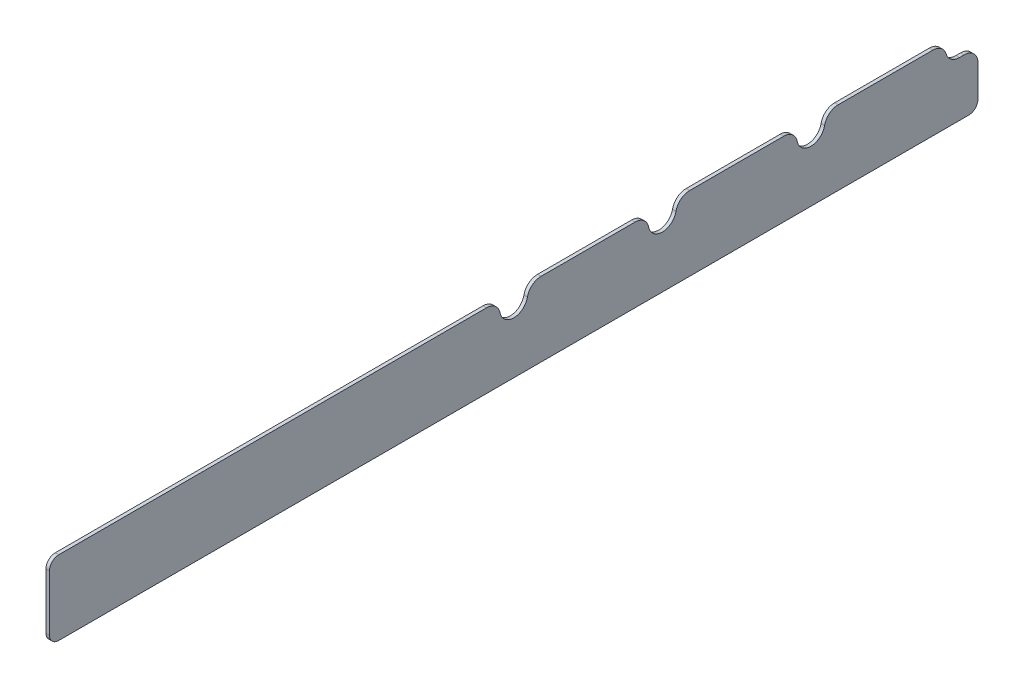
SolidWorks part; units mm, degrees
material "Plain Carbon Steel"
ref_plane "Front" through (0, 0, 0) normal (0, 0, 1) x (1, 0, 0)
ref_plane "Top" through (0, 0, 0) normal (0, 1, 0) x (1, 0, 0)
ref_plane "Right" through (0, 0, 0) normal (1, 0, 0) x (0, 0, -1)
sketch "Sketch1" plane through (0, 0, 0) normal (1, 0, 0) x (0, 0, -1)
  line L1 (-158.75, -12.7) -> (158.75, -12.7)
  line L2 (-158.75, -12.7) -> (-158.75, 12.7)
  line L3 (-158.75, 12.7) -> (158.75, 12.7)
  line L4 (158.75, -12.7) -> (158.75, 12.7)
  line L5 (-158.75, -12.7) -> (158.75, 12.7) construction
  line L6 (-158.75, 12.7) -> (158.75, -12.7) construction
  point P0 (0, 0)
  dimension "D1" = 25.4
  dimension "D2" = 317.5
base flange "Base-Flange1" sketch "Sketch1" thickness 1.1938 reverse thickness direction no parameters "D1"=1.4986
fillet "Fillet1" radius 3.175 4 edges at (-0.5969, 12.7, -158.75) (-0.5969, -12.7, 158.75) (-0.5969, -12.7, -158.75) (-0.5969, 12.7, 158.75)
sketch "Sketch2" plane through (-1.1938, 0, 0) normal (-1, 0, 0) x (0, 0, 1)
  line L0 (-155.575, 12.7) -> (155.575, 12.7) construction
  line L1 (-4.7625, 9.8298) -> (-4.7625, 12.7)
  line L2 (4.7625, 9.8298) -> (4.7625, 12.7)
  line L3 (-4.7625, 12.7) -> (4.7625, 12.7)
  arc A0 (-4.7625, 9.8298) -> (4.7625, 9.8298) centre (0, 9.8298) ccw
  arc A1 (3.8004, 12.7) -> (-3.8004, 12.7) centre (0, 9.8298) ccw construction
  arc A2 (-3.8004, 12.7) -> (-4.7625, 9.8298) centre (0, 9.8298) ccw construction
  arc A3 (4.7625, 9.8298) -> (3.8004, 12.7) centre (0, 9.8298) ccw construction
  point P1 (-10.9415, 9.8298)
  point P3 (0, 0)
  dimension "D3" = 9.525
  dimension "D1" = 2.8702
extrude "Cut-Extrude1" cut sketch "Sketch2" against normal through all normal cut yes
fillet "Fillet2" radius 4.7625 2 edges at (-0.5969, 12.7, 4.7625) (-0.5969, 12.7, -4.7625)
pattern_linear "LPattern2" count 3 spacing 50.8 along (0, 0, -1) of "Cut-Extrude1", "Fillet2"
sketch "Sketch3" plane through (-1.1938, 0, 0) normal (-1, 0, 0) x (0, 0, 1)
  line L0 (-155.575, 12.7) -> (-110.9351, 12.7) construction
  line L1 (-152.4, 5.9512) -> (-158.75, 5.9512)
  line L2 (-158.75, -9.525) -> (-158.75, 9.525) construction
  line L3 (-147.6375, 10.7137) -> (-147.6375, 12.7)
  line L4 (-155.575, 12.7) -> (-147.6375, 12.7)
  line L5 (-158.75, 5.9512) -> (-158.75, 9.525)
  line L6 (-147.6375, 12.7) -> (-110.9351, 12.7) construction
  line L7 (-158.75, -9.525) -> (-158.75, 5.9512) construction
  arc A0 (-152.4, 5.9512) -> (-147.6375, 10.7137) centre (-152.4, 10.7137) ccw
  arc A2 (-155.575, 12.7) -> (-158.75, 9.525) centre (-155.575, 9.525) ccw construction
  arc A3 (-155.575, 12.7) -> (-158.75, 9.525) centre (-155.575, 9.525) ccw
  arc A4 (-154.6162, 6.4982) -> (-152.4, 5.9512) centre (-152.4, 10.7137) ccw construction
  arc A5 (-148.0715, 12.7) -> (-154.6162, 6.4982) centre (-152.4, 10.7137) ccw construction
  arc A6 (-147.6375, 10.7137) -> (-148.0715, 12.7) centre (-152.4, 10.7137) ccw construction
  arc A7 (-106.2676, 8.8836) -> (-96.9324, 8.8836) centre (-101.6, 9.8298) ccw construction
  point P10 (-101.6, 5.0673)
  dimension "D2" = 9.525
  dimension "D1" = 1.9863
  dimension "D3" = 50.8
extrude "Cut-Extrude2" cut sketch "Sketch3" against normal through all normal cut yes
fillet "Fillet3" radius 4.7625 2 edges at (-0.5969, 5.9512, -158.75) (-0.5969, 12.7, -147.6375)
sketch "Bend-Lines1" [suppressed] plane through (0, 0, 0) normal (0, 1, 0) x (1, 0, 0)
sketch "Bounding-Box1" [suppressed] plane through (0, 0, 0) normal (0, 1, 0) x (1, 0, 0)
sheet metal parameters "Sheet-Metal28" thickness 1.1938 parameters "D1"=1.4986
flat pattern "Flat-Pattern28" [suppressed]
sketch "Bend-Lines2" plane through (0, 0, 0) normal (0, 1, 0) x (1, 0, 0)
sketch3d "Bounding-Box2" [suppressed]
  line L0 (177.8, -12.7, 0) -> (-177.8, -12.7, 0) construction
  line L1 (177.8, 12.7, 0) -> (-177.8, 12.7, 0) construction
  line L2 (177.8, -12.7, 0) -> (177.8, 12.7, 0) construction
  line L3 (-177.8, -12.7, 0) -> (-177.8, 12.7, 0) construction
sheet metal parameters "Sheet-Metal29" thickness 1.1938 parameters "D1"=1.4986
flat pattern "Flat-Pattern28"
sketch "Bend-Lines2" plane through (0, 0, 0) normal (0, 1, 0) x (1, 0, 0)
sketch3d "Bounding-Box2" [suppressed]
  line L0 (177.8, -12.7, 0) -> (-177.8, -12.7, 0) construction
  line L1 (177.8, 12.7, 0) -> (-177.8, 12.7, 0) construction
  line L2 (177.8, -12.7, 0) -> (177.8, 12.7, 0) construction
  line L3 (-177.8, -12.7, 0) -> (-177.8, 12.7, 0) construction
sheet metal parameters "Sheet-Metal30" thickness 1.1938 parameters "D1"=1.4986
flat pattern "Flat-Pattern28"
sketch "Bend-Lines2" plane through (0, 0, 0) normal (0, 1, 0) x (1, 0, 0)
sketch3d "Bounding-Box2" [suppressed]
  line L0 (158.75, -12.7, 0) -> (-158.75, -12.7, 0) construction
  line L1 (158.75, 12.7, 0) -> (-158.75, 12.7, 0) construction
  line L2 (158.75, -12.7, 0) -> (158.75, 12.7, 0) construction
  line L3 (-158.75, -12.7, 0) -> (-158.75, 12.7, 0) construction
sheet metal parameters "Sheet-Metal31" thickness 1.1938 parameters "D1"=1.4986
flat pattern "Flat-Pattern28"
sketch "Bend-Lines2" plane through (0, 0, 0) normal (0, 1, 0) x (1, 0, 0)
sketch3d "Bounding-Box2" [suppressed]
  line L0 (158.75, 12.7002, 0) -> (-158.75, 12.7, 0) construction
  line L1 (158.75, -12.6998, 0) -> (-158.75, -12.7, 0) construction
  line L2 (158.75, 12.7002, 0) -> (158.75, -12.6998, 0) construction
  line L3 (-158.75, 12.7, 0) -> (-158.75, -12.7, 0) construction
equation "\"Total Cutting Length\"= \"Cutting Length-Outer\" + \"Cutting Length-Inner\""
equation "\"Amount in ft^2\"= \"Bounding Box Area-Blank\" / 144"
